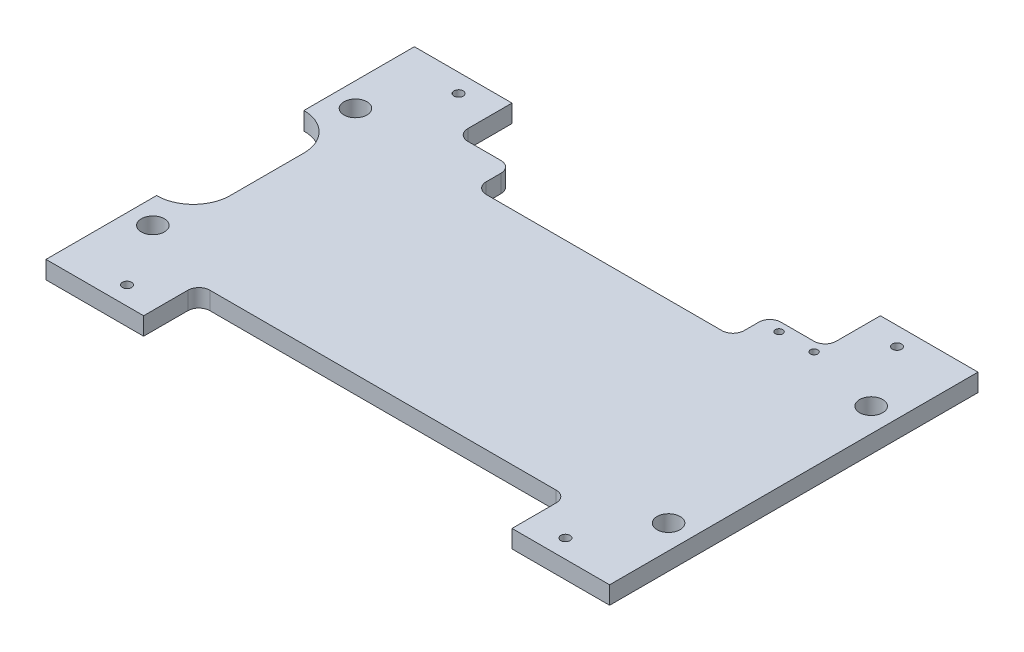
SolidWorks part; units mm, degrees
ref_plane "Front Plane" through (0, 0, 0) normal (0, 0, 1) x (1, 0, 0)
ref_plane "Top Plane" through (0, 0, 0) normal (0, 1, 0) x (1, 0, 0)
ref_plane "Right Plane" through (0, 0, 0) normal (1, 0, 0) x (0, 0, -1)
sketch "Sketch1" plane through (0, 0, 0) normal (0, 1, 0) x (1, 0, 0)
  line L0 (-76.5, 50) -> (76.5, -50) construction
  line L1 (-76.5, 50) -> (76.5, 50)
  line L2 (-76.5, 50) -> (-76.5, -50)
  line L3 (-76.5, -50) -> (76.5, -50)
  line L4 (76.5, 50) -> (76.5, -50)
  dimension "D1" = 100
  dimension "D2" = 153
extrude "Boss-Extrude1" add sketch "Sketch1" along normal blind 4.826
sketch "Sketch2" plane through (0, 4.826, 0) normal (0, 1, 0) x (1, 0, 0)
  line L0 (76.5, 50) -> (-76.5, 50) construction
  line L1 (-50, 50) -> (50, 50)
  line L2 (-50, 50) -> (-50, 35)
  line L3 (-50, 35) -> (50, 35)
  line L4 (50, 50) -> (50, 35)
  line L5 (-76.5, 0) -> (76.5, 0) construction
  line L6 (-76.5, 50) -> (-76.5, -50) construction
  line L7 (76.5, -50) -> (76.5, 50) construction
  line L8 (0, 35) -> (0, 0) construction
  line L9 (50, -50) -> (50, -35)
  line L10 (-50, -35) -> (50, -35)
  line L11 (-50, -50) -> (-50, -35)
  line L12 (-50, -50) -> (50, -50)
  dimension "D1" = 15
  dimension "D2" = 100
extrude "Cut-Extrude1" cut sketch "Sketch2" against normal through all
sketch "Sketch3" plane through (0, 4.826, 0) normal (0, 1, 0) x (1, 0, 0)
  line L0 (0, 35) -> (0, -35) construction
  line L1 (-50, 35) -> (50, 35) construction
  line L2 (50, -35) -> (-50, -35) construction
  line L3 (-70, 50) -> (-70, -50) construction
  line L4 (-50, 50) -> (-76.5, 50) construction
  line L5 (-76.5, -50) -> (-50, -50) construction
  line L6 (-76.5, 0) -> (-70, 0) construction
  line L7 (-76.5, 50) -> (-76.5, -50) construction
  line L8 (-59.5, 50) -> (-59.5, -50) construction
  circle A0 centre (-70, 27.5) radius 3.125
  circle A1 centre (-70, -27.5) radius 3.125
  circle A2 centre (70, -27.5) radius 3.125
  circle A3 centre (70, 27.5) radius 3.125
  circle A4 centre (-59.5, 45) radius 1.25
  circle A5 centre (-59.5, -45) radius 1.25
  circle A6 centre (59.5, 45) radius 1.25
  circle A7 centre (59.5, -45) radius 1.25
  dimension "D2" = 55
  dimension "D3" = 6.25
  dimension "D5" = 2.5
  dimension "D4" = 119
  dimension "D1" = 70
  dimension "D6" = 5
extrude "Cut-Extrude2" cut sketch "Sketch3" against normal through all
sketch "Sketch5" plane through (0, 4.826, 0) normal (0, 1, 0) x (1, 0, 0)
  line L1 (-76.5, 50) -> (-76.5, -50) construction
  line L2 (-76.5, 20) -> (-66.5, 20)
  line L3 (-76.5, 20) -> (-76.5, -20)
  line L4 (-76.5, -20) -> (-66.5, -20)
  line L5 (-66.5, 20) -> (-66.5, -20)
  line L6 (-66.5, 0) -> (0, 0) construction
  dimension "D1" = 10
  dimension "D2" = 40
extrude "Cut-Extrude3" cut sketch "Sketch5" against normal through all
sketch "Sketch6" plane through (0, 4.826, 0) normal (0, 1, 0) x (1, 0, 0)
  line L0 (40, 32.5) -> (49.5, 32.5) construction
  line L1 (0, 0) -> (0, 25) construction
  line L2 (-50, 35) -> (50, 35) construction
  line L3 (-35, 35) -> (35, 35)
  line L4 (-35, 35) -> (-35, 25)
  line L5 (-35, 25) -> (35, 25)
  line L6 (35, 35) -> (35, 25)
  circle A0 centre (40, 32.5) radius 1
  circle A1 centre (49.5, 32.5) radius 1
  dimension "D2" = 2
  dimension "D1" = 9.5
  dimension "D3" = 2.5
  dimension "D4" = 40
  dimension "D5" = 10
  dimension "D6" = 70
extrude "Cut-Extrude4" cut sketch "Sketch6" against normal through all
fillet "Fillet1" radius 3 8 edges at (-50, 2.413, 35) (50, 2.413, 35) (50, 2.413, -35) (-50, 2.413, -35) (35, 2.413, -35) (35, 2.413, -25) (-35, 2.413, -25) (-35, 2.413, -35)
fillet "Fillet2" radius 10 2 edges at (-66.5, 2.413, 20) (-66.5, 2.413, -20)
